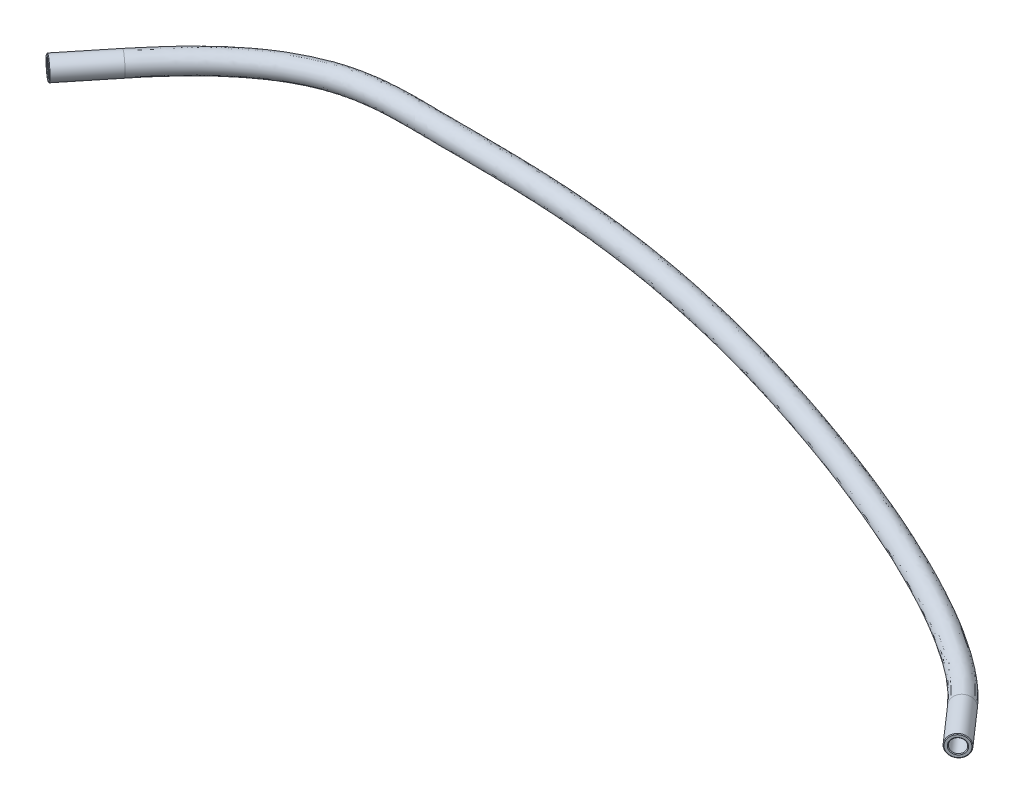
SolidWorks part; units mm, degrees
ref_plane "Front Plane" through (0, 0, 0) normal (0, 0, 1) x (1, 0, 0)
ref_plane "Top Plane" through (0, 0, 0) normal (0, 1, 0) x (1, 0, 0)
ref_plane "Right Plane" through (0, 0, 0) normal (1, 0, 0) x (0, 0, -1)
sketch3d "3DSketch1"
  line L0 (-120.0726, -99.5875, -21.9249) -> (-126.4864, -99.5875, -13.9938)
  line L1 (70.1644, -99.6875, 10.8405) -> (64.1041, -99.6875, 3.9186)
  spline S0 degree 3 poles (64.1041, -99.6875, 3.9186) (52.305, -99.6875, -9.5581) (-27.9783, -99.6522, -42.8291) (-78.2287, -99.6022, -40.2685) (-103.8226, -99.5875, -42.019) (-120.0726, -99.5875, -21.9249) knots 0 0 0 0 0.304238 0.705959 1 1 1 1
sketch "Sketch1" plane through (31.1417, 0, 35.5692) normal (-0.6587, 0, -0.7524) x (-0.7524, 0, 0.6587)
  circle A0 centre (-45.6494, -99.6875) radius 2
  circle A1 centre (-45.6494, -99.6875) radius 1.3
  circle A3 centre (-45.6494, -99.6875) radius 3.5524 construction
  dimension "D1" = 2.6
  dimension "D2" = 4
sweep "Sweep1" add profiles "Sketch1" path "3DSketch1"
chamfer "Chamfer1" distance 0.127 angle 45 4 edges at (-124.9313, -99.589, -12.7362) (-125.4756, -99.5884, -13.1764) (68.6597, -99.6875, 12.158) (69.1863, -99.6875, 11.6968)
